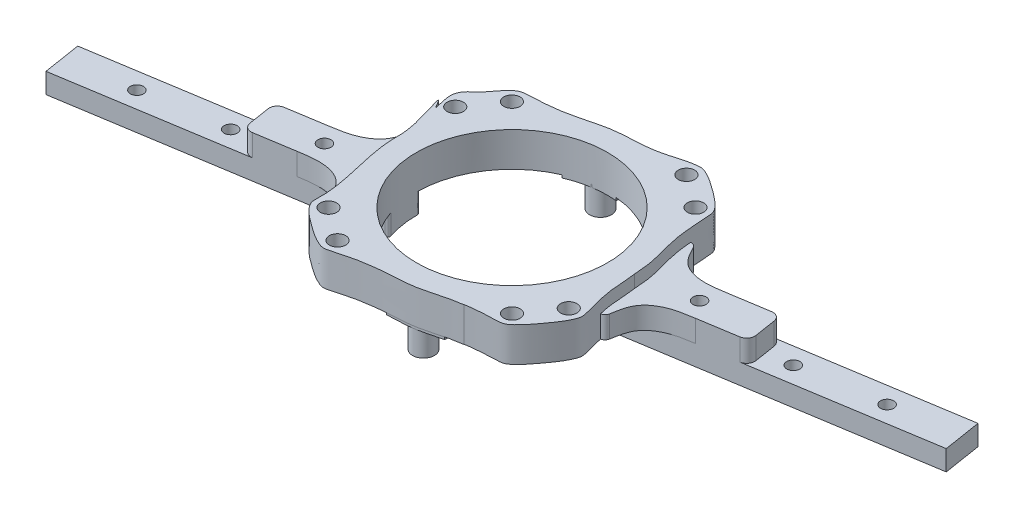
SolidWorks part; units mm, degrees
ref_plane "前视基准面" through (0, 0, 0) normal (0, 0, 1) x (1, 0, 0)
ref_plane "上视基准面" through (0, 0, 0) normal (0, 1, 0) x (1, 0, 0)
ref_plane "右视基准面" through (0, 0, 0) normal (1, 0, 0) x (0, 0, -1)
sketch "草图1" plane through (0, 0, 0) normal (0, 1, 0) x (1, 0, 0)
  circle A0 centre (0, 0) radius 17.5
  circle A1 centre (0, 0) radius 18.901
  dimension "D1" = 35
extrude "凸台-拉伸1" add sketch "草图1" along normal blind 2
sketch "草图2" plane through (0, 0, 0) normal (0, -1, 0) x (1, 0, 0)
  circle A0 centre (-10.7739, 21.1656) radius 1.5
  circle A1 centre (16.8004, 16.7872) radius 1.5
  circle A2 centre (21.1656, 10.7739) radius 1.5
  circle A3 centre (16.7872, -16.8004) radius 1.5
  circle A4 centre (10.7739, -21.1656) radius 1.5
  circle A5 centre (-16.8004, -16.7872) radius 1.5
  circle A6 centre (-21.1656, -10.7739) radius 1.5
  circle A7 centre (-16.7872, 16.8004) radius 1.5
  circle A28 centre (0, 0) radius 17.5
  spline S3 degree 3 poles (11.007, 19.7796) (11.3114, 19.6784) (14.2307, 19.3249) (16.1426, 19.3879) (17.8124, 19.1708) (19.4344, 17.903) (21.2548, 15.4236) (23.0457, 12.9332) (23.7495, 10.9887) (23.274, 8.5261) (21.9734, 4.7628) (22.0269, 1.1873) (21.7447, -0.683) knots 0 0 0 0 0.101498 0.202996 0.236379 0.269761 0.41266 0.555558 0.58894 0.622323 0.811161 1 1 1 1
  spline S4 degree 3 poles (21.7447, -0.683) (21.6101, -1.5752) (21.6055, -3.3542) (20.6884, -6.8809) (19.4904, -11.3054) (19.4855, -15.3122) (19.178, -17.8032) (17.9056, -19.4334) (15.4365, -21.2528) (12.9718, -22.9922) (11.1783, -23.6905) (8.6855, -23.5473) (4.924, -21.9674) (0.2192, -21.8124) (-3.3386, -21.5662) (-6.4463, -20.811) (-9.0785, -20.0903) (-12.7412, -19.4848) (-15.1253, -19.3752) (-17.5836, -19.2474) (-19.4002, -18.127) (-20.9244, -15.1209) (-24.3676, -13.3124) (-22.2966, -7.7817) (-24.7387, -12.2711) (-21.435, -3.3276) (-22.0126, 0.3206) (-20.5515, 8.1406) (-19.1109, 13.0019) (-19.2816, 16.8284) knots 0 0 0 0 0.02817 0.053916 0.112305 0.168269 0.178162 0.188055 0.230405 0.272754 0.280796 0.288838 0.34856 0.404524 0.432694 0.45844 0.502911 0.516855 0.572819 0.576577 0.592462 0.634812 0.677161 0.707499 0.719914 0.775878 0.831843 0.888071 1 1 1 1
  spline S5 degree 3 poles (-19.2816, 16.8284) (-19.323, 17.5174) (-18.1907, 19.2578) (-15.4061, 21.2421) (-12.9273, 23.0421) (-10.9838, 23.7431) (-9.3566, 23.4387) (-7.2233, 22.7077) (-4.4614, 22.2162) (-1.8337, 21.8607) (0.7732, 21.7432) (3.3794, 21.5754) (7.3403, 20.5662) (8.6858, 20.19) (9.8558, 19.9936) (10.7406, 19.8682) (11.007, 19.7796) knots 0 0 0 0 0.047987 0.150696 0.253406 0.277399 0.301393 0.374345 0.447298 0.510152 0.573007 0.641327 0.709648 0.853023 0.882058 1 1 1 1
  dimension "D1" = 3
extrude "凸台-拉伸2" add sketch "草图2" along normal blind 4.3 and the other way blind 2
sketch "草图3" plane through (0, -4.3, 0) normal (0, -1, 0) x (1, 0, 0)
  line L0 (7.3484, 9.4647) -> (-44.5797, 17.7103) construction
  line L1 (3.0581, 19.2587) -> (0, 0) construction
  line L2 (0, 0) -> (-3.0579, -19.2577) construction
  line L3 (-7.4518, -9.4473) -> (44.4763, -17.6928) construction
  circle A0 centre (3.0581, 19.2587) radius 2
  circle A1 centre (3.0581, 19.2587) radius 9 construction
  circle A2 centre (-3.0579, -19.2577) radius 2
  circle A3 centre (-3.0579, -19.2577) radius 9 construction
  dimension "D1" = 18
  dimension "D2" = 4
  dimension "D3" = 18
  dimension "D4" = 4
extrude "凸台-拉伸3" add sketch "草图3" along normal blind 5
sketch "草图5" plane through (0, -4.3, 0) normal (0, -1, 0) x (1, 0, 0)
  line L0 (0, 0) -> (38.9853, -6.1904) construction
  line L1 (70.6703, -14.0546) -> (-71.5479, 8.5279) construction
  circle A0 centre (3.0581, 19.2587) radius 5 construction
  arc A1 (-1.5944, 17.4272) -> (6.9144, 16.0761) centre (0, 0) cw
  arc A2 (-2.6852, -17.2928) -> (2.7444, 17.2835) centre (0, 0) ccw construction
  arc A3 (-1.3158, 21.6815) -> (-1.5944, 17.4272) centre (3.0581, 19.2587) ccw
  arc A4 (7.9454, 20.3141) -> (6.9144, 16.0761) centre (3.0581, 19.2587) cw
  arc A5 (-7.9672, -20.2075) -> (-6.9144, -16.0761) centre (-3.0581, -19.2587) cw
  arc A6 (-6.9144, -16.0761) -> (1.5944, -17.4272) centre (0, 0) ccw
  arc A7 (1.262, -21.7761) -> (1.5944, -17.4272) centre (-3.0581, -19.2587) ccw
  spline S0 degree 3 poles (-1.3158, 21.6815) (-0.2135, 21.5939) (1.3807, 21.5885) (3.4585, 21.3907) (5.444, 20.9684) (6.9168, 20.5202) (7.9454, 20.3141) knots 0 0 0 0 0.352817 0.508743 0.665414 1 1 1 1
  spline S2 degree 3 poles (-7.9672, -20.2075) (-6.892, -20.4656) (-5.3746, -20.9543) (-3.3377, -21.4099) (-1.319, -21.6234) (0.2201, -21.6535) (1.262, -21.7761) knots 0 0 0 0 0.352817 0.508743 0.665414 1 1 1 1
  dimension "D1" = 10
extrude "凸台-拉伸5" add sketch "草图5" along normal blind 0.5
sketch "草图6" plane through (0, -4.3, 0) normal (0, -1, 0) x (1, 0, 0)
  line L0 (0, 0) -> (83.2876, -13.2251) construction
  line L1 (70.6703, -14.0546) -> (-71.5479, 8.5279) construction
  line L2 (0, 0) -> (7.0837, 44.6111) construction
  line L3 (22.6545, 6.4264) -> (16.7134, 7.3698)
  line L4 (32.0065, -1.5404) -> (39.048, -2.6585)
  line L5 (71.6577, -7.8366) -> (-70.5606, 14.746) construction
  line L6 (-30.9094, 8.4499) -> (-37.9509, 9.5679)
  line L7 (40.2942, -4.3752) -> (39.9809, -6.3485)
  line L8 (19.5496, -13.1279) -> (13.6084, -12.1845)
  line L9 (30.9094, -8.4499) -> (37.9509, -9.5679)
  line L10 (39.6675, -8.3217) -> (39.9809, -6.3485)
  line L11 (-39.6675, 8.3217) -> (-39.9809, 6.3485)
  line L12 (-40.2942, 4.3752) -> (-39.9809, 6.3485)
  line L13 (-32.0065, 1.5404) -> (-39.048, 2.6585)
  line L14 (-19.5496, 13.1279) -> (-13.6084, 12.1845)
  line L15 (-22.6545, -6.4264) -> (-16.7134, -7.3698)
  circle A0 centre (21.1656, 10.7739) radius 2.5 construction
  arc A1 (1.5944, -17.4272) -> (6.9144, 16.0761) centre (0, 0) ccw construction
  arc A2 (13.3066, -11.3659) -> (16.1729, 6.685) centre (0, 0) ccw
  arc A3 (23.4842, 5.6027) -> (22.6545, 6.4264) centre (22.4977, 5.4388) ccw
  arc A4 (16.7134, 7.3698) -> (16.1729, 6.685) centre (16.6349, 6.876) ccw
  arc A5 (39.048, -2.6585) -> (40.2942, -4.3752) centre (38.8128, -4.14) cw
  arc A6 (13.6084, -12.1845) -> (13.3066, -11.3659) centre (13.6868, -11.6907) cw
  arc A7 (20.5935, -12.6017) -> (19.5496, -13.1279) centre (19.7064, -12.1402) cw
  arc A8 (37.9509, -9.5679) -> (39.6675, -8.3217) centre (38.1861, -8.0865) ccw
  arc A9 (-37.9509, 9.5679) -> (-39.6675, 8.3217) centre (-38.1861, 8.0865) ccw
  arc A10 (-39.048, 2.6585) -> (-40.2942, 4.3752) centre (-38.8128, 4.14) cw
  arc A11 (-20.5935, 12.6017) -> (-19.5496, 13.1279) centre (-19.7064, 12.1402) cw
  arc A12 (-13.6084, 12.1845) -> (-13.3066, 11.3659) centre (-13.6868, 11.6907) cw
  arc A13 (-16.1729, -6.685) -> (-13.3066, 11.3659) centre (0, 0) cw
  arc A14 (-16.7134, -7.3698) -> (-16.1729, -6.685) centre (-16.6349, -6.876) ccw
  arc A15 (-23.4842, -5.6027) -> (-22.6545, -6.4264) centre (-22.6575, -5.5997) ccw
  spline S0 degree 3 poles (20.5935, -12.6017) (20.8165, -12.1731) (21.4171, -11.0059) (22.8603, -8.9685) (26.5188, -7.7575) (29.1956, -8.1777) (30.9094, -8.4499) knots 0.057026 0.057026 0.057026 0.057026 0.169435 0.36028 0.616457 1 1 1 1
  spline S1 degree 3 poles (23.4842, 5.6027) (23.5634, 5.1261) (23.7729, 3.8302) (24.514, 1.446) (27.6174, -0.8387) (30.2927, -1.2683) (32.0065, -1.5404) knots 0.057026 0.057026 0.057026 0.057026 0.169435 0.36028 0.616457 1 1 1 1
  spline S2 degree 3 poles (-23.4842, -5.6027) (-23.5634, -5.1261) (-23.7729, -3.8302) (-24.514, -1.446) (-27.6174, 0.8387) (-30.2927, 1.2683) (-32.0065, 1.5404) knots 0.057026 0.057026 0.057026 0.057026 0.169435 0.36028 0.616457 1 1 1 1
  spline S3 degree 3 poles (-20.5935, 12.6017) (-20.8165, 12.1731) (-21.4171, 11.0059) (-22.8603, 8.9685) (-26.5188, 7.7575) (-29.1956, 8.1777) (-30.9094, 8.4499) knots 0.057026 0.057026 0.057026 0.057026 0.169435 0.36028 0.616457 1 1 1 1
  point P34 (15.8047, 7.514)
  dimension "D1" = 5
  dimension "D2" = 1
  dimension "D3" = 0.5
  dimension "D4" = 1.5
extrude "凸台-拉伸6" add sketch "草图6" against normal blind 4 separate body
sketch "草图7" plane through (0, -4.3, 0) normal (0, -1, 0) x (1, 0, 0)
  line L0 (17.2287, -6.2775) -> (70.5606, -14.746)
  line L1 (17.2287, -6.2775) -> (18.3258, 0.6319) construction
  line L2 (70.5606, -14.746) -> (71.6577, -7.8366)
  line L3 (18.3258, 0.6319) -> (71.6577, -7.8366)
  line L4 (17.2287, -6.2775) -> (71.6577, -7.8366) construction
  line L5 (70.5606, -14.746) -> (18.3258, 0.6319) construction
  line L6 (71.6577, -7.8366) -> (-70.5606, 14.746) construction
  line L7 (71.6266, -8.0321) -> (70.5916, -14.5504) construction
  line L8 (18.3258, 0.6319) -> (18.0775, 0.6713)
  line L9 (17.2287, -6.2775) -> (16.9804, -6.2381)
  line L10 (70.5606, -14.746) -> (-71.6577, 7.8366) construction
  line L11 (0, 0) -> (5.947, 37.4527) construction
  line L12 (-71.6577, 7.8366) -> (-70.5606, 14.746)
  line L13 (-17.2287, 6.2775) -> (-70.5606, 14.746)
  line L14 (-18.3258, -0.6319) -> (-71.6577, 7.8366)
  line L15 (-18.3258, -0.6319) -> (-18.0775, -0.6713)
  line L16 (-17.2287, 6.2775) -> (-16.9804, 6.2381)
  arc A0 (1.5944, -17.4272) -> (6.9144, 16.0761) centre (0, 0) ccw construction
  arc A1 (17.4991, 0.1726) -> (16.585, -5.5847) centre (0, 0) cw
  arc A2 (16.9804, -6.2381) -> (16.585, -5.5847) centre (17.0588, -5.7443) cw
  arc A3 (18.0775, 0.6713) -> (17.4991, 0.1726) centre (17.9991, 0.1775) ccw
  arc A4 (-18.0775, -0.6713) -> (-17.4991, -0.1726) centre (-17.9991, -0.1775) ccw
  arc A5 (-16.9804, 6.2381) -> (-16.585, 5.5847) centre (-17.0588, 5.7443) cw
  arc A6 (-16.585, 5.5847) -> (-17.4991, -0.1726) centre (0, 0) ccw
  point P1 (44.4432, -7.057)
  point P20 (16.3861, -6.1437)
  point P23 (17.4832, 0.7657)
  dimension "D1" = 0.5
extrude "凸台-拉伸7" add sketch "草图7" along normal up to surface (3.7 mm away)
sketch "草图8" plane through (0, -8, 0) normal (0, -1, 0) x (1, 0, 0)
  circle A0 centre (59.2576, -9.4094) radius 1.2
  circle A1 centre (44.4432, -7.057) radius 1.2
  circle A2 centre (29.6288, -4.7047) radius 1.2
  circle A3 centre (-29.6288, 4.7047) radius 1.2
  circle A4 centre (-44.4432, 7.057) radius 1.2
  circle A5 centre (-59.2576, 9.4094) radius 1.2
  dimension "D1" = 2.4
extrude "切除-拉伸1" cut sketch "草图8" against normal through all
